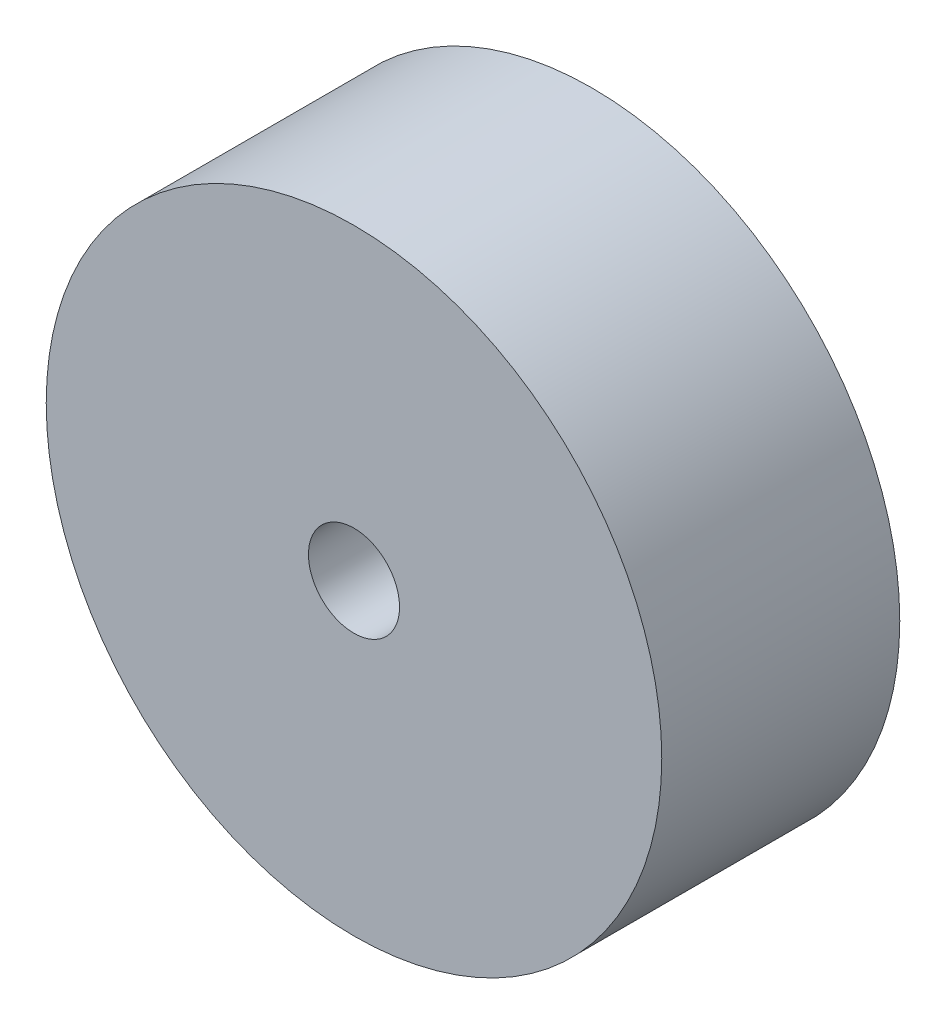
SolidWorks part; units mm, degrees
ref_plane "Front Plane" through (0, 0, 0) normal (0, 0, 1) x (1, 0, 0)
ref_plane "Top Plane" through (0, 0, 0) normal (0, 1, 0) x (1, 0, 0)
ref_plane "Right Plane" through (0, 0, 0) normal (1, 0, 0) x (0, 0, -1)
sketch "Sketch1" plane through (0, 0, 0) normal (0, 0, 1) x (1, 0, 0)
  circle A0 centre (-29.0823, -1.7038) radius 7.5
  dimension "D1" = 15
extrude "Boss-Extrude1" add sketch "Sketch1" along normal blind 5.8
sketch "Sketch2" plane through (0, 0, 0) normal (0, 0, -1) x (-1, 0, 0)
  circle A0 centre (29.0823, -1.7038) radius 6.325
  dimension "D1" = 12.65
extrude "Cut-Extrude1" cut sketch "Sketch2" against normal blind 1.5875
sketch "Sketch3" plane through (0, 0, 1.5875) normal (0, 0, -1) x (-1, 0, 0)
  circle A0 centre (29.0823, -1.7038) radius 1
  dimension "D1" = 2
extrude "Boss-Extrude2" add sketch "Sketch3" along normal blind 1.5875
sketch "Sketch4" plane through (0, 0, 0) normal (0, 0, -1) x (-1, 0, 0)
  circle A0 centre (29.0823, -1.7038) radius 3.15
  dimension "D1" = 6.3
extrude "Boss-Extrude3" add sketch "Sketch4" against normal blind 3
sketch "Sketch5" plane through (0, 0, 0) normal (0, 0, -1) x (-1, 0, 0)
  circle A0 centre (29.0823, -1.7038) radius 0.85
  dimension "D1" = 1.7
extrude "Cut-Extrude2" cut sketch "Sketch5" against normal through all
sketch "Sketch6" plane through (0, 0, 5.8) normal (0, 0, 1) x (1, 0, 0)
  circle A0 centre (-29.0823, -1.7038) radius 1.11
  dimension "D1" = 2.22
extrude "Cut-Extrude3" cut sketch "Sketch6" against normal blind 3
